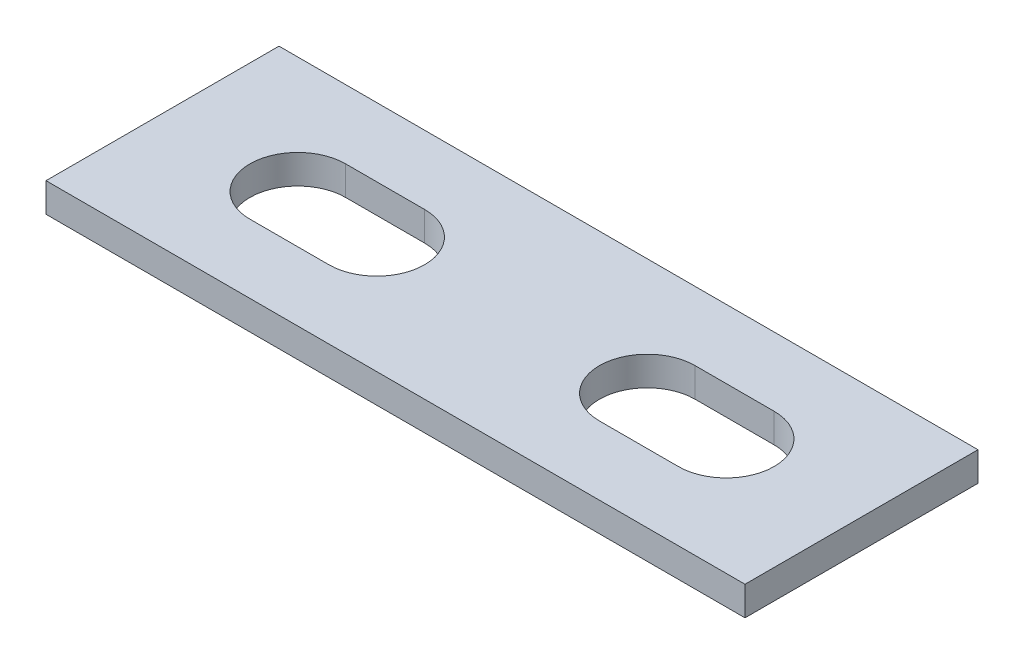
SolidWorks part; units mm, degrees
ref_plane "Front" through (0, 0, 0) normal (0, 0, 1) x (1, 0, 0)
ref_plane "Top" through (0, 0, 0) normal (0, 1, 0) x (1, 0, 0)
ref_plane "Right" through (0, 0, 0) normal (1, 0, 0) x (0, 0, -1)
sketch "Sketch1" plane through (0, 0, 0) normal (0, 1, 0) x (1, 0, 0)
  line L0 (-38.1, 0) -> (38.1, 0) construction
  line L1 (-38.1, 12.7) -> (38.1, 12.7)
  line L2 (-38.1, 12.7) -> (-38.1, -12.7)
  line L3 (-38.1, -12.7) -> (38.1, -12.7)
  line L4 (38.1, 12.7) -> (38.1, -12.7)
  line L5 (-38.1, 12.7) -> (38.1, -12.7) construction
  line L6 (-38.1, -12.7) -> (38.1, 12.7) construction
  line L7 (-23.3553, 0) -> (-14.7447, 0) construction
  line L8 (-23.3553, 5.2197) -> (-14.7447, 5.2197)
  line L9 (-23.3553, -5.2197) -> (-14.7447, -5.2197)
  line L10 (0, 0) -> (0, 12.7) construction
  line L11 (23.3553, 0) -> (14.7447, 0) construction
  line L12 (23.3553, 5.2197) -> (14.7447, 5.2197)
  line L13 (23.3553, -5.2197) -> (14.7447, -5.2197)
  arc A0 (-23.3553, 5.2197) -> (-23.3553, -5.2197) centre (-23.3553, 0) ccw
  arc A1 (-14.7447, -5.2197) -> (-14.7447, 5.2197) centre (-14.7447, 0) ccw
  arc A2 (23.3553, 5.2197) -> (23.3553, -5.2197) centre (23.3553, 0) cw
  arc A3 (14.7447, -5.2197) -> (14.7447, 5.2197) centre (14.7447, 0) cw
  point P0 (0, 0)
  point P10 (-19.05, 0)
  point P19 (19.05, 0)
  dimension "D3" = 19.05
  dimension "D1" = 76.2
  dimension "D2" = 25.4
  dimension "D4" = 10.4394
  dimension "D5" = 38.1
extrude "Boss-Extrude1" add sketch "Sketch1" along normal blind 3.175
ref_axis "Axis1" through (-23.3553, 3.175, 0) along (0, -1, 0)
